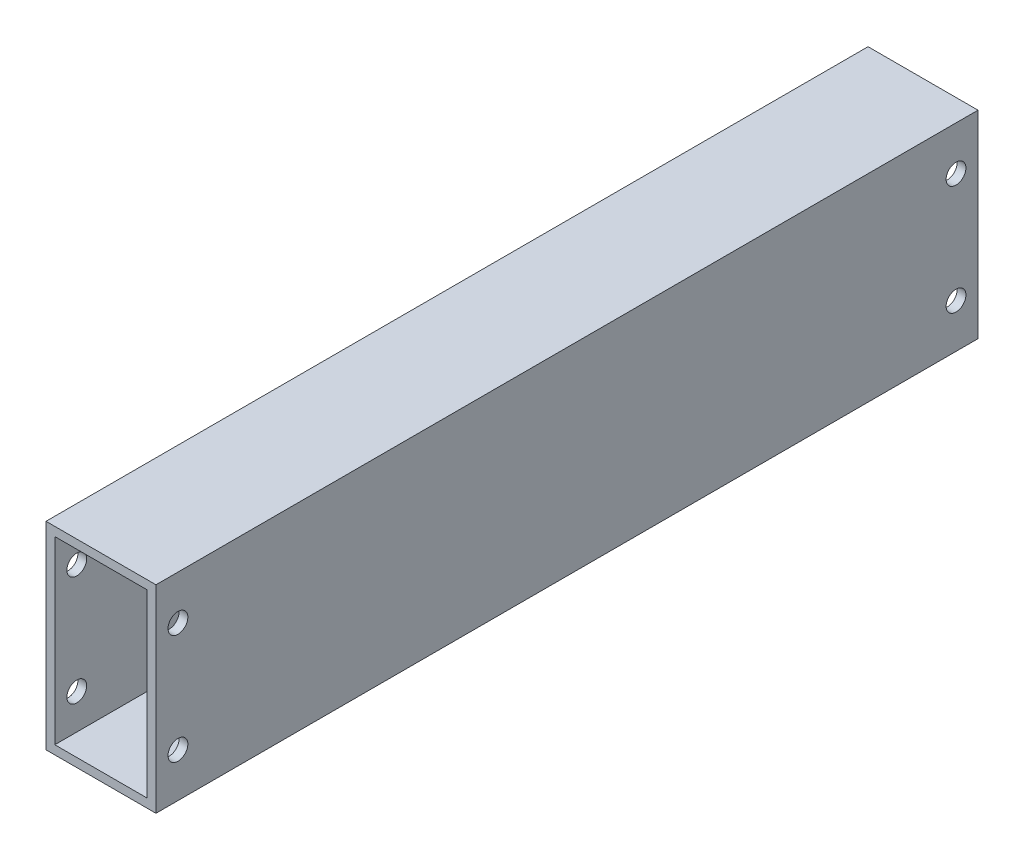
SolidWorks part; units mm, degrees
note: '?' marks a value the reader was unsure of.
material "3.3547 (EN-AW 5083)"
ref_plane "Front Plane" through (0, 0, 0) normal (0, 0, 1) x (1, 0, 0)
ref_plane "Top Plane" through (0, 0, 0) normal (0, 1, 0) x (1, 0, 0)
ref_plane "Right Plane" through (0, 0, 0) normal (1, 0, 0) x (0, 0, -1)
ref_axis "Axis1" through (0, 0, 236.245) along (0, 0, -1)?
ref_plane "Plane1" through (0, 0, 40) normal (0, 0, 1) x (1, 0, 0)
ref_axis "Wrist" through (0, -29.3693, 287.9) along (0, 1, 0)?
ref_plane "Plane2" through (0, 0, 287.9) normal (0, 0, 1) x (1, 0, 0)
ref_plane "Plane3" through (0, 0, 226.9) normal (0, 0, 1) x (1, 0, 0)
ref_point "Point2"
sketch "Sketch1" plane through (0, 0, 40) normal (0, 0, 1) x (1, 0, 0)
  line L0 (12.5, 22.5) -> (-12.5, 22.5) construction
  line L1 (12.5, -22.5) -> (-12.5, -22.5)
  line L2 (12.5, -22.5) -> (12.5, 22.5)
  line L3 (12.5, 22.5) -> (-12.5, 22.5)
  line L4 (-12.5, -22.5) -> (-12.5, 22.5)
  line L5 (12.5, -22.5) -> (-12.5, 22.5) construction
  line L6 (12.5, 22.5) -> (-12.5, -22.5) construction
  line L7 (-12.5, 22.5) -> (-12.5, -22.5) construction
  line L8 (10.5, -20.5) -> (10.5, 20.5)
  line L9 (10.5, 20.5) -> (-10.5, 20.5)
  line L10 (-10.5, -20.5) -> (-10.5, 20.5)
  line L11 (10.5, -20.5) -> (-10.5, -20.5)
  circle A0 centre (0, 0) radius 25.7391 construction
  point P0 (0, 0)
  dimension "D2" = 51.4782
  dimension "D1" = 2
extrude "Boss-Extrude1" add sketch "Sketch1" along normal up to vertex (186.9 mm away)
sketch "Sketch4" plane through (12.5, 0, 0) normal (1, 0, 0) x (0, 0, -1)
  point P13 (-45, -12.5)
  point P16 (-45, 12.5)
  point P19 (-221.9, 12.5)
  point P22 (-221.9, -12.5)
hole_wizard "M4 Clearance Hole1" positions "Sketch4" profile "Sketch3" hole size "M4" standard "DIN" end condition through all
sketch "Sketch3" plane through (12.5, -12.5, 45) normal (0, 1, 0) x (0, 0, -1)
  line L0 (0, 0) -> (0, 25)
  line L1 (0, 25) -> (2.25, 25)
  line L2 (2.25, 25) -> (2.25, 0)
  line L5 (2.25, 0) -> (0, 0)
  line L11 (0, -6.35) -> (0, 107.95) construction
  dimension "Thru Hole Dia." = 4.5
  dimension "Thru Hole Depth" = 25
